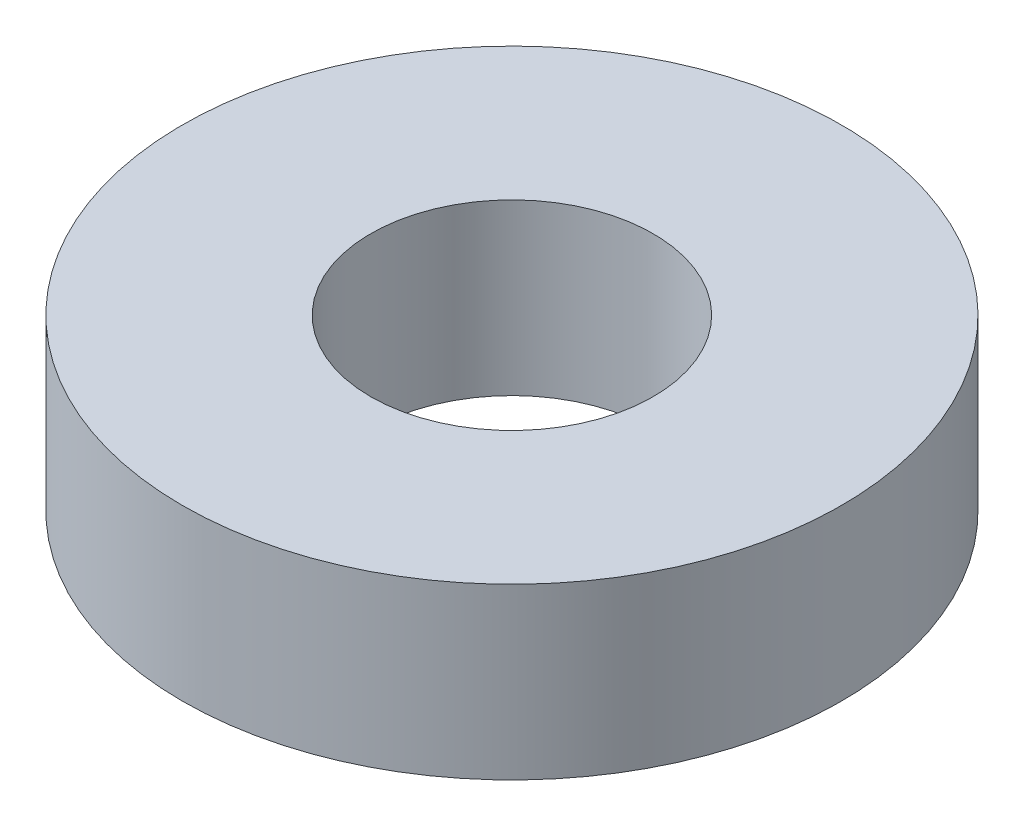
SolidWorks part; units mm, degrees
ref_plane "Front Plane" through (0, 0, 0) normal (0, 0, 1) x (1, 0, 0)
ref_plane "Top Plane" through (0, 0, 0) normal (0, 1, 0) x (1, 0, 0)
ref_plane "Right Plane" through (0, 0, 0) normal (1, 0, 0) x (0, 0, -1)
sketch "Sketch1" plane through (0, 0, 0) normal (0, 1, 0) x (1, 0, 0)
  circle A0 centre (0, 0) radius 35
  dimension "FLANGE_OD" = 70
extrude "Boss-Extrude1" add sketch "Sketch1" along normal blind 18
sketch "Sketch2" plane through (0, 0, 0) normal (0, 1, 0) x (1, 0, 0)
  circle A0 centre (0, 0) radius 15
  dimension "BORE_D" = 30
extrude "Cut-Extrude1" cut sketch "Sketch2" along normal through all
sketch "Sketch3" plane through (0, 18, 0) normal (0, 1, 0) x (1, 0, 0)
  circle A0 centre (0, 0) radius 11.4784 construction
  circle A1 centre (-11.4784, 0) radius 2.1308
  dimension "BOLT_D" = 4.2615
  dimension "BOLT_PCD" = 22.9568
extrude "Cut-Extrude2" cut sketch "Sketch3" against normal blind 17.2087 rebuild error yes
pattern_circular "CirPattern1" count 3 over 360 rebuild error yes
